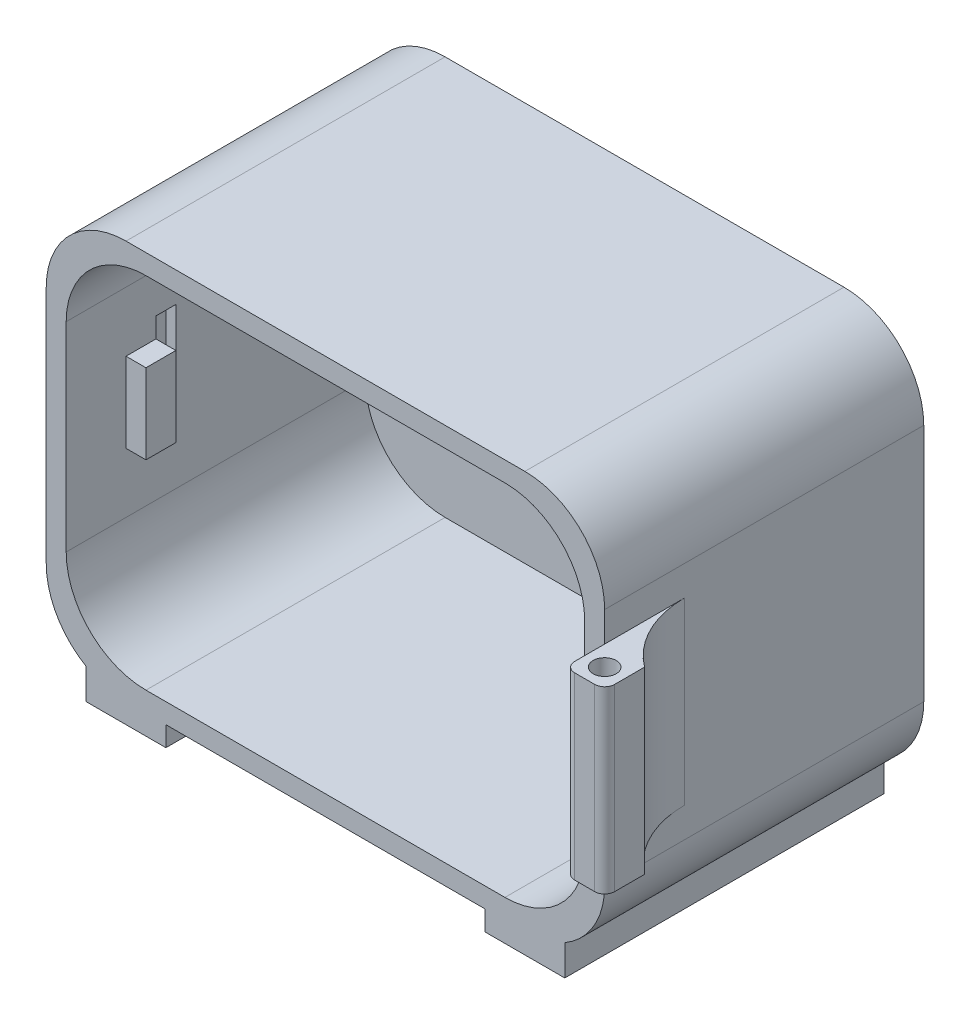
SolidWorks part; units mm, degrees
ref_plane "Front Plane" through (0, 0, 0) normal (0, 0, 1) x (1, 0, 0)
ref_plane "Top Plane" through (0, 0, 0) normal (0, 1, 0) x (1, 0, 0)
ref_plane "Right Plane" through (0, 0, 0) normal (1, 0, 0) x (0, 0, -1)
sketch "Sketch1" plane through (0, 0, 0) normal (0, 0, 1) x (1, 0, 0)
  line L0 (-82.55, 31.75) -> (-82.55, -31.75)
  line L1 (-63.5, 63.5) -> (63.5, 63.5)
  line L2 (-88.9, 38.1) -> (-88.9, -38.1)
  line L3 (-63.5, -63.5) -> (63.5, -63.5)
  line L4 (88.9, 38.1) -> (88.9, -38.1)
  line L5 (-88.9, 63.5) -> (88.9, -63.5) construction
  line L6 (-88.9, -63.5) -> (88.9, 63.5) construction
  line L7 (-57.15, -57.15) -> (57.15, -57.15)
  line L8 (82.55, 31.75) -> (82.55, -31.75)
  line L9 (-57.15, 57.15) -> (57.15, 57.15)
  line L10 (-88.9, 63.5) -> (88.9, 63.5) construction
  line L11 (88.9, 63.5) -> (88.9, -63.5) construction
  line L12 (82.55, 57.15) -> (82.55, -57.15) construction
  line L13 (-82.55, 57.15) -> (82.55, 57.15) construction
  line L14 (-82.55, -57.15) -> (82.55, -57.15) construction
  line L15 (-88.9, -63.5) -> (88.9, -63.5) construction
  line L16 (-82.55, 57.15) -> (-82.55, -57.15) construction
  line L17 (-88.9, 63.5) -> (-88.9, -63.5) construction
  arc A0 (63.5, 63.5) -> (88.9, 38.1) centre (63.5, 38.1) cw
  arc A1 (82.55, 31.75) -> (57.15, 57.15) centre (57.15, 31.75) ccw
  arc A2 (57.15, -57.15) -> (82.55, -31.75) centre (57.15, -31.75) ccw
  arc A3 (63.5, -63.5) -> (88.9, -38.1) centre (63.5, -38.1) ccw
  arc A4 (-82.55, -31.75) -> (-57.15, -57.15) centre (-57.15, -31.75) ccw
  arc A5 (-88.9, -38.1) -> (-63.5, -63.5) centre (-63.5, -38.1) ccw
  arc A6 (-63.5, 63.5) -> (-88.9, 38.1) centre (-63.5, 38.1) ccw
  arc A7 (-82.55, 31.75) -> (-57.15, 57.15) centre (-57.15, 31.75) cw
  point P0 (0, 0)
  dimension "D4" = 25.4
  dimension "D1" = 177.8
  dimension "D2" = 127
  dimension "D3" = 6.35
extrude "Boss-Extrude1" add sketch "Sketch1" against normal blind 95.25
sketch "Sketch2" plane through (0, 0, -95.25) normal (0, 0, -1) x (-1, 0, 0)
  line L0 (-63.5, 63.5) -> (63.5, 63.5)
  line L1 (-63.5, 63.5) -> (63.5, 63.5) construction
  line L2 (0, 63.5) -> (0, -63.5) construction
  line L3 (63.5, -63.5) -> (-63.5, -63.5) construction
  line L4 (63.5, -63.5) -> (-63.5, -63.5)
  line L5 (-88.9, -38.1) -> (-88.9, 38.1) construction
  line L6 (-88.9, -38.1) -> (-88.9, 38.1)
  line L7 (88.9, -38.1) -> (88.9, 38.1)
  arc A0 (-88.9, 38.1) -> (-63.5, 63.5) centre (-63.5, 38.1) cw
  arc A1 (-63.5, -63.5) -> (-88.9, -38.1) centre (-63.5, -38.1) cw
  arc A2 (-88.9, -38.1) -> (-63.5, -63.5) centre (-63.5, -38.1) ccw construction
  arc A3 (63.5, -63.5) -> (88.9, -38.1) centre (63.5, -38.1) ccw
  arc A4 (88.9, 38.1) -> (63.5, 63.5) centre (63.5, 38.1) ccw
extrude "Boss-Extrude2" add sketch "Sketch2" along normal blind 6.35
sketch "Sketch4" plane through (0, -63.5, 0) normal (0, -1, 0) x (1, 0, 0)
  line L0 (-76.2, 0) -> (-50.8, 0)
  line L2 (-76.2, 0) -> (-76.2, -101.6)
  line L3 (-88.9, -101.6) -> (-63.5, -101.6) construction
  line L4 (-76.2, -101.6) -> (-50.8, -101.6)
  line L5 (63.5, -101.6) -> (-63.5, -101.6) construction
  line L6 (-50.8, -101.6) -> (-50.8, 0)
  line L7 (0, 0) -> (0, -101.6) construction
  line L8 (-63.5, 0) -> (63.5, 0) construction
  line L9 (76.2, -101.6) -> (50.8, -101.6)
  line L10 (76.2, 0) -> (76.2, -101.6)
  line L11 (76.2, 0) -> (50.8, 0)
  line L12 (50.8, -101.6) -> (50.8, 0)
  point P4 (-63.5, 0)
  dimension "D1" = 25.4
extrude "Boss-Extrude3" add sketch "Sketch4" along normal blind 6.35 and the other way up to next
sketch "Sketch5" plane through (0, 0, 0) normal (0, 1, 0) x (1, 0, 0)
  line L0 (0, 0) -> (88.9, 0) construction
  line L1 (63.5, 0) -> (-63.5, 0) construction
  line L2 (95.25, 0) -> (101.6, 0) construction
  line L3 (88.9, 25.4) -> (88.9, 0)
  line L4 (95.25, 0) -> (95.25, -6.35) construction
  line L7 (101.6, -12.7) -> (88.9, -12.7)
  line L8 (101.6, -12.7) -> (101.6, 0)
  line L9 (101.6, 0) -> (95.25, 0)
  line L10 (88.9, -12.7) -> (88.9, 0)
  line L11 (101.6, -12.7) -> (88.9, 0) construction
  line L12 (101.6, 0) -> (88.9, -12.7) construction
  line L13 (88.9, -6.35) -> (101.6, -6.35) construction
  arc A3 (101.6, 0) -> (88.9, 25.4) centre (120.65, 25.4) cw
  circle A4 centre (95.25, -6.35) radius 3.675
  point P4 (98.425, 0)
  dimension "D2" = 7.35
  dimension "D1" = 6.35
  dimension "D3" = 88.9
  dimension "D4" = 25.4
extrude "Boss-Extrude5" add sketch "Sketch5" along normal blind 28.575 and the other way blind 28.575 contours A3 L3 L10 L7 L8 A4 region at (94.0273, 0, 0.7656)
fillet "Fillet1" radius 3.175 1 edges at (101.6, 0, 12.7)
sketch "Sketch6" plane through (0, 28.575, 0) normal (0, 1, 0) x (1, 0, 0)
  line L0 (91.575, -6.35) -> (88.9, -6.35) construction
  line L1 (88.9, 0) -> (88.9, -12.7) construction
  line L2 (97.1007, -9.525) -> (101.6, -9.525) construction
  circle A0 centre (95.25, -6.35) radius 3.675 construction
sketch "Sketch8" plane through (-82.55, 0, 0) normal (1, 0, 0) x (0, 0, -1)
  line L0 (0, -19.05) -> (28.575, -19.05) construction
  line L1 (0, 31.75) -> (0, -31.75) construction
  line L2 (28.575, -19.05) -> (34.925, -19.05)
  line L3 (34.925, -19.05) -> (34.925, 19.05)
  line L4 (34.925, 19.05) -> (28.575, 19.05)
  line L5 (28.575, 19.05) -> (28.575, -19.05)
  line L6 (95.25, -57.15) -> (0, -57.15) construction
  dimension "D1" = 28.575
  dimension "D2" = 6.35
  dimension "D3" = 38.1
  dimension "D4" = 38.1
extrude "Cut-Extrude1" cut sketch "Sketch8" against normal blind 3.175
sketch "Sketch10" plane through (-82.55, 0, 0) normal (1, 0, 0) x (0, 0, -1)
  line L0 (28.575, 0) -> (28.575, 12.7) construction
  line L1 (28.575, 19.05) -> (28.575, -19.05) construction
  line L3 (28.575, 12.7) -> (19.05, 12.7)
  line L4 (28.575, 12.7) -> (28.575, -12.7)
  line L5 (28.575, -12.7) -> (19.05, -12.7)
  line L6 (19.05, 12.7) -> (19.05, -12.7)
  point P7 (28.575, 0)
  dimension "D1" = 12.7
  dimension "D2" = 9.525
extrude "Boss-Extrude6" add sketch "Sketch10" along normal blind 6.35
sketch "Sketch11" plane through (0, 0, -101.6) normal (0, 0, -1) x (-1, 0, 0)
  line L0 (32.462, -188.0741) -> (352.462, -188.0741) construction
  line L1 (-8.558, 38.2776) -> (9.4147, 38.2776)
  line L2 (9.4147, 38.2776) -> (12.3761, 30.5166)
  line L3 (12.3761, 30.5166) -> (6.5554, 30.5166)
  line L4 (-8.558, 38.2776) -> (-26.541, -14.1457)
  line L5 (-26.541, -14.1457) -> (-20.9531, -14.1457)
  line L6 (-20.9531, -17.5278) -> (-27.8644, -17.5278)
  line L7 (-27.8644, -17.5278) -> (-30.0702, -24.7333)
  line L8 (-30.0702, -24.7333) -> (-9.6303, -24.7333)
  line L9 (-9.6303, -24.7333) -> (-7.4245, -17.5278)
  line L10 (-7.4245, -17.5278) -> (8.4569, -17.5278)
  line L11 (8.4569, -17.5278) -> (10.5156, -24.7333)
  line L12 (10.5156, -24.7333) -> (12.3761, -24.7333)
  line L13 (12.3761, -24.7333) -> (12.3761, -18.8513)
  line L14 (16.1034, -18.8513) -> (16.1034, -24.7333)
  line L15 (16.1034, -24.7333) -> (21.2502, -24.7333)
  line L16 (21.2502, -24.7333) -> (21.2502, -18.8513)
  line L17 (24.3382, -18.8513) -> (24.3382, -24.7333)
  line L18 (24.3382, -24.7333) -> (31.2496, -24.7333)
  line L19 (31.2496, -24.7333) -> (13.3095, 27.1753)
  line L20 (13.3095, 27.1753) -> (6.5554, 27.1753)
  line L21 (0.7548, 15.0295) -> (-4.8523, -6.6891)
  line L22 (-4.8523, -6.6891) -> (6.0184, -6.6891)
  line L23 (6.0184, -6.6891) -> (0.7548, 15.0295)
  arc A0 (6.5554, 30.5166) -> (6.5554, 27.1753) centre (2.9252, 28.8459) ccw
  arc A1 (12.3761, -18.8513) -> (16.1034, -18.8513) centre (14.2398, -15.2135) cw
  arc A2 (-20.9531, -14.1457) -> (-20.9531, -17.5278) centre (-17.0513, -15.8368) cw
  arc A3 (21.2502, -18.8513) -> (24.3382, -18.8513) centre (22.7942, -15.1977) cw
  circle A4 centre (2.9252, 28.8459) radius 1.6706
  circle A5 centre (-17.0513, -15.8368) radius 2.045
  circle A6 centre (14.2398, -15.2135) radius 2.3144
  circle A7 centre (22.7942, -15.1977) radius 1.5563
  circle A8 centre (0, 3.175) radius 44.8241
  dimension "D1" = 3.175
extrude "Cut-Extrude4" cut sketch "Sketch11" against normal blind 1.5875 contours A8 | L22 L23 L21 | A3 L17 L18 L19 L20 A0 L3 L2 L1 L4 L5 A2 L6 L7 L8 L9 L10 L11 L12 L13 A1 L14 L15 L16
sketch "Sketch12" plane through (0, 0, -101.6) normal (0, 0, -1) x (-1, 0, 0)
  line L0 (0, 0) -> (0, -57.15) construction
  line L1 (63.5, -57.15) -> (-63.5, -57.15) construction
  text T0 "amp-lab.org" font "Century Gothic" height in points 48
  point P6 (0, -57.15)
  dimension "D1" = 57.15
  dimension "D2" = 127
extrude "Cut-Extrude5" cut sketch "Sketch12" against normal blind 1.5875
fillet "Fillet2" radius 3.175 1 edges at (88.9, 0, 12.7)
